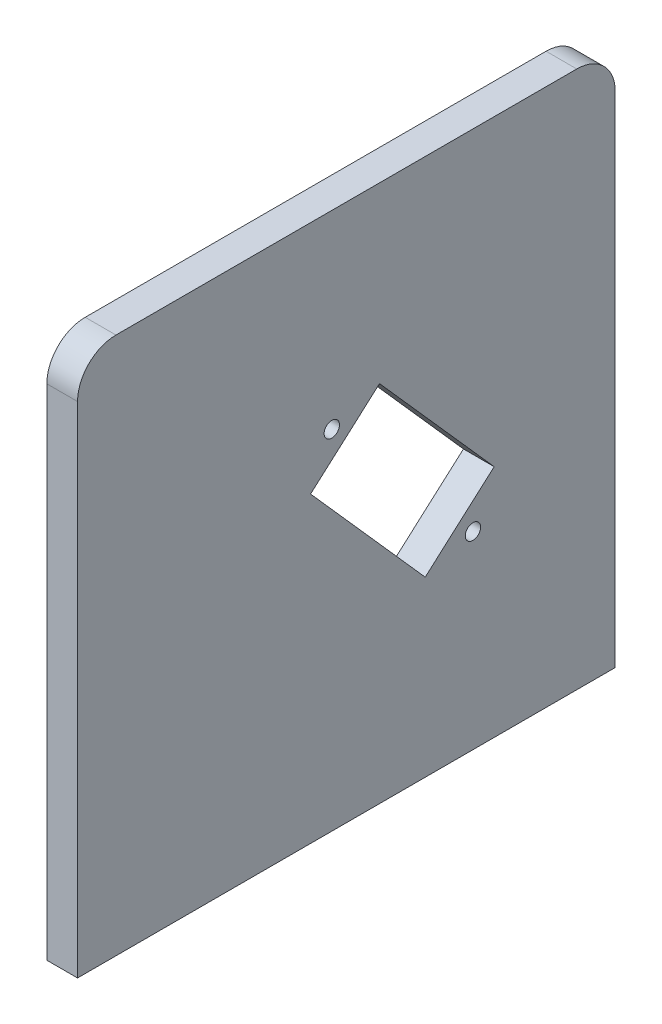
SolidWorks part; units mm, degrees
ref_plane "Front Plane" through (0, 0, 0) normal (0, 0, 1) x (1, 0, 0)
ref_plane "Top Plane" through (0, 0, 0) normal (0, 1, 0) x (1, 0, 0)
ref_plane "Right Plane" through (0, 0, 0) normal (1, 0, 0) x (0, 0, -1)
sketch "Sketch1" plane through (0, 0, 0) normal (0, 1, 0) x (1, 0, 0)
  line L5 (39.2287, 39.2125) -> (39.2287, -30.7875)
  line L9 (39.2287, 39.2125) -> (35.2287, 39.2125)
  line L10 (35.2287, 39.2125) -> (35.2287, -30.7875)
  line L11 (35.2287, -30.7875) -> (39.2287, -30.7875)
  dimension "D6" = 4
extrude "Boss-Extrude1" add sketch "Sketch1" along normal blind 3 contours L11 L10 L9 | L10 L11 L9 region at (37.2287, 0, -4.2125)
extrude "Boss-Extrude2" add sketch "Sketch1<3>" along normal blind 70
sketch "Sketch1<3>" plane through (0, 0, 0) normal (0, 1, 0) x (1, 0, 0) same geometry as "Sketch1"
extrude "Boss-Extrude3" add sketch "Sketch1<4>" along normal blind 70 rebuild error yes
sketch "Sketch1<4>" plane through (0, 0, 0) normal (0, 1, 0) x (1, 0, 0) same geometry as "Sketch1"
sketch "Sketch5" plane through (-50.7713, 0, 0) normal (-1, 0, 0) x (0, 0, 1)
  line L0 (-8.0225, 70) -> (-8.0225, 0) construction
  line L5 (-34.2125, 70) -> (-34.2125, 3) construction
  circle A0 centre (-8.0225, 60) radius 4
  dimension "D1" = 60
  dimension "D3" = 8
  dimension "D2" = 26.19
extrude "Cut-Extrude4" cut sketch "Sketch5" against normal blind 10 rebuild error yes
sketch "Sketch6" plane through (0, 3, 0) normal (0, 1, 0) x (1, 0, 0)
  line L0 (-50.7876, 44.2125) -> (49.2124, 44.2125) construction
  line L3 (-50.7876, -35.7875) -> (49.2124, -35.7875) construction
  line L8 (-50.7713, -40.7875) -> (39.2287, -40.7875) construction
  line L9 (-50.7713, 49.2125) -> (39.2287, 49.2125) construction
  circle A0 centre (-45.7876, -35.7875) radius 2.5
  circle A1 centre (-45.7876, 44.2125) radius 2.5
  circle A2 centre (43.7185, 44.2125) radius 2.5
  circle A3 centre (43.7185, -35.7875) radius 2.5
  dimension "D1" = 5
  dimension "D2" = 5
  dimension "D3" = 5
  dimension "D4" = 5
extrude "Cut-Extrude5" cut sketch "Sketch6" against normal blind 10 rebuild error yes
extrude "Boss-Extrude4" add sketch "Sketch1<5>" along normal blind 80 rebuild error yes
sketch "Sketch1<5>" plane through (0, 0, 0) normal (0, 1, 0) x (1, 0, 0) same geometry as "Sketch1"
extrude "Cut-Extrude6" cut sketch "Sketch5<2>" against normal blind 10 rebuild error yes
sketch "Sketch5<2>" plane through (-50.7713, 0, 0) normal (-1, 0, 0) x (0, 0, 1) same geometry as "Sketch5"
fillet "Fillet1" radius 3 rebuild error yes
fillet "Fillet2" radius 5 2 edges at (37.2287, 70, -39.2125) (37.2287, 70, 30.7875)
fillet "Fillet3" radius 4 rebuild error yes
sketch "Sketch7" plane through (39.2287, 0, 0) normal (1, 0, 0) x (0, 0, -1)
  line L0 (-30.7875, -10) -> (39.2125, -10) construction
  line L1 (-30.7875, 65) -> (-30.7875, 0) construction
  line L2 (39.2125, 65) -> (39.2125, 0) construction
  line L3 (-37.7875, 0) -> (46.2125, 0) construction
  circle A0 centre (27.4823, -10) radius 2.5
  dimension "D1" = 10
extrude "Cut-Extrude7" cut sketch "Sketch7" against normal blind 10 rebuild error yes
sketch "Sketch8" plane through (39.2287, 0, 0) normal (1, 0, 0) x (0, 0, -1)
  line L0 (39.2125, 20) -> (-30.7875, 20) construction
  line L1 (39.2125, 65) -> (39.2125, 0) construction
  line L2 (-30.7875, 65) -> (-30.7875, 0) construction
  line L3 (26.9146, 20) -> (8.0207, 38.8939) construction
  circle A0 centre (8.0207, 38.8939) radius 2.5
  dimension "D3" = 5
  dimension "D1" = 26.72
  dimension "D2" = 45
extrude "Cut-Extrude8" cut sketch "Sketch8" against normal blind 10
sketch "Sketch9" plane through (39.2287, 0, 0) normal (1, 0, 0) x (0, 0, -1)
  circle A1 centre (8.0207, 38.8939) radius 3.5
extrude "Cut-Extrude9" cut sketch "Sketch9" against normal up to surface (67.5 mm away) rebuild error yes
sketch "Sketch26" plane through (0, 3, 0) normal (0, 1, 0) x (1, 0, 0)
  line L0 (39.2287, 39.2125) -> (39.2287, 46.2125) construction
  line L1 (39.2287, -37.7875) -> (39.2287, -30.7875) construction
  circle A0 centre (34.2287, 44.2125) radius 2.5
  circle A2 centre (34.2287, -36.0634) radius 2.5
  dimension "D1" = 5
  dimension "D2" = 5
  dimension "D3" = 5
  dimension "D4" = 5
extrude "Cut-Extrude11" cut sketch "Sketch26" against normal blind 10 contours A2 | A0 rebuild error yes
sketch "Sketch27" plane through (0, 3, 0) normal (0, 1, 0) x (1, 0, 0)
  line L0 (-49.8926, 48.3339) -> (38.35, -39.9088) construction
  line L1 (38.35, 48.3339) -> (-49.8926, -39.9088) construction
  line L2 (7.7287, 4.2125) -> (-19.2713, 4.2125) construction
  line L3 (7.7287, 3.4625) -> (-19.2713, 3.4625)
  line L4 (7.7287, 4.9625) -> (-19.2713, 4.9625)
  line L5 (0.9787, -7.4788) -> (-12.5213, 15.9039) construction
  line L6 (0.3292, -7.8538) -> (-13.1708, 15.5289)
  line L7 (1.6282, -7.1038) -> (-11.8718, 16.2789)
  line L8 (-12.5213, -7.4788) -> (0.9787, 15.9039) construction
  line L9 (-13.1708, -7.1038) -> (0.3292, 16.2789)
  line L10 (-11.8718, -7.8538) -> (1.6282, 15.5289)
  line L11 (-19.2713, 4.2125) -> (7.7287, 4.2125) construction
  line L12 (-19.2713, 4.9625) -> (7.7287, 4.9625)
  line L13 (-19.2713, 3.4625) -> (7.7287, 3.4625)
  line L14 (-12.5213, 15.9039) -> (0.9787, -7.4788) construction
  line L15 (-11.8718, 16.2789) -> (1.6282, -7.1038)
  line L16 (-13.1708, 15.5289) -> (0.3292, -7.8538)
  line L17 (0.9787, 15.9039) -> (-12.5213, -7.4788) construction
  line L18 (1.6282, 15.5289) -> (-11.8718, -7.8538)
  line L19 (0.3292, 16.2789) -> (-13.1708, -7.1038)
  arc A0 (-47.7713, 49.2125) -> (-50.7713, 46.2125) centre (-47.7713, 46.2125) ccw construction
  arc A1 (36.2287, -40.7875) -> (39.2287, -37.7875) centre (36.2287, -37.7875) ccw construction
  arc A2 (39.2287, 46.2125) -> (36.2287, 49.2125) centre (36.2287, 46.2125) ccw construction
  arc A3 (-50.7713, -37.7875) -> (-47.7713, -40.7875) centre (-47.7713, -37.7875) ccw construction
  arc A4 (7.7287, 3.4625) -> (7.7287, 4.9625) centre (7.7287, 4.2125) ccw
  arc A5 (-19.2713, 4.9625) -> (-19.2713, 3.4625) centre (-19.2713, 4.2125) ccw
  circle A9 centre (-5.7713, 4.2125) radius 5.375
  arc A10 (0.3292, -7.8538) -> (1.6282, -7.1038) centre (0.9787, -7.4788) ccw
  arc A11 (-11.8718, 16.2789) -> (-13.1708, 15.5289) centre (-12.5213, 15.9039) ccw
  arc A12 (-13.1708, -7.1038) -> (-11.8718, -7.8538) centre (-12.5213, -7.4788) ccw
  arc A13 (1.6282, 15.5289) -> (0.3292, 16.2789) centre (0.9787, 15.9039) ccw
  arc A14 (-19.2713, 4.9625) -> (-19.2713, 3.4625) centre (-19.2713, 4.2125) ccw
  arc A15 (7.7287, 3.4625) -> (7.7287, 4.9625) centre (7.7287, 4.2125) ccw
  arc A16 (-11.8718, 16.2789) -> (-13.1708, 15.5289) centre (-12.5213, 15.9039) ccw
  arc A17 (0.3292, -7.8538) -> (1.6282, -7.1038) centre (0.9787, -7.4788) ccw
  arc A18 (1.6282, 15.5289) -> (0.3292, 16.2789) centre (0.9787, 15.9039) ccw
  arc A19 (-13.1708, -7.1038) -> (-11.8718, -7.8538) centre (-12.5213, -7.4788) ccw
  circle A20 centre (-5.7713, 4.2125) radius 2.75
  point P18 (-5.7713, 4.2125)
  point P30 (-5.7713, 4.2125)
  point P37 (-5.7713, 4.2125)
  point P44 (-5.7713, 4.2125)
  point P51 (-5.7713, 4.2125)
  point P58 (-5.7713, 4.2125)
  point P63 (-5.7713, 4.2125)
  dimension "D1" = 10.75
  dimension "D2" = 0.75
  dimension "D3" = 13.5
  dimension "D4" = 6
extrude "Cut-Extrude14" cut sketch "Sketch27" against normal blind 10 contours L3 A5 L4 A4 | L6 A11 L7 A10 | L10 A13 L9 A12 rebuild error yes
extrude "Cut-Extrude15" cut sketch "Sketch27<7>" against normal blind 10 contours L3 A20 L9 | L6 A20 L4 | L9 A20 L7 | L4 A20 L10 | L7 A20 L3 | L10 A20 L6 rebuild error yes
sketch "Sketch27<7>" plane through (0, 3, 0) normal (0, 1, 0) x (1, 0, 0) same geometry as "Sketch27"
sketch "Sketch28" plane through (-50.7713, 0, 0) normal (-1, 0, 0) x (0, 0, 1)
  line L0 (-23.4588, 51.635) -> (-8.5312, 68.47)
  line L1 (-8.5312, 68.47) -> (0.4475, 60.5086)
  line L2 (0.4475, 60.5086) -> (-14.4801, 43.6736)
  line L3 (-14.4801, 43.6736) -> (-23.4588, 51.635)
  line L4 (-8.0225, 60) -> (-12.6884, 54.7379) construction
  line L5 (-12.6884, 54.7379) -> (-25.2505, 40.5707) construction
  line L6 (-8.0225, 60) -> (2.1094, 71.4266) construction
  circle A0 centre (-8.0225, 60) radius 4 construction
  circle A1 centre (-8.0225, 60) radius 4
  circle A2 centre (-2.3169, 66.4347) radius 1
  circle A3 centre (-20.6944, 45.709) radius 1
  point P8 (-18.9694, 47.6543)
  dimension "D3" = 2
  dimension "D4" = 8.6
  dimension "D5" = 27.7
  dimension "D1" = 22.5
  dimension "D2" = 12
  dimension "D6" = 2.6
extrude "Cut-Extrude16" cut sketch "Sketch28" against normal up to surface (4 mm away) rebuild error yes
sketch "Sketch29" plane through (39.2287, 0, 0) normal (1, 0, 0) x (0, 0, -1)
  line L8 (8.0207, 38.8939) -> (0.0593, 47.8726) construction
  line L9 (0.0593, 47.8726) -> (37.8759, 5.2239) construction
  line L10 (8.5294, 47.3639) -> (23.457, 30.5289)
  line L11 (23.457, 30.5289) -> (14.4783, 22.5675)
  line L12 (14.4783, 22.5675) -> (-0.4493, 39.4025)
  line L13 (-0.4493, 39.4025) -> (8.5294, 47.3639)
  circle A6 centre (8.0207, 38.8939) radius 3.5 construction
  circle A7 centre (8.0207, 38.8939) radius 3.5
  circle A8 centre (2.3151, 45.3286) radius 1
  circle A9 centre (20.6926, 24.6028) radius 1
  point P4 (4.04, 43.3832)
  point P28 (18.9676, 26.5482)
  dimension "D4" = 2.6
  dimension "D5" = 27.7
  dimension "D6" = 2
  dimension "D7" = 2
  dimension "D2" = 12
  dimension "D3" = 22.5
  dimension "D8" = 8.6
extrude "Cut-Extrude18" cut sketch "Sketch29" against normal up to surface (4 mm away) up to face at (35.2287, 38.8939, -10.5207)
sketch "Sketch31" plane through (0, 3, 0) normal (0, 1, 0) x (1, 0, 0)
  circle A0 centre (-5.7713, 4.2125) radius 5.375
  dimension "D1" = 10.75
extrude "Cut-Extrude19" cut sketch "Sketch31" against normal blind 10 rebuild error yes
sketch "Sketch33" plane through (39.2287, 0, 0) normal (1, 0, 0) x (0, 0, -1)
  circle A0 centre (8.0207, 38.8939) radius 3.5 construction
  circle A1 centre (8.0207, 38.8939) radius 3.5
extrude "Cut-Extrude20" cut sketch "Sketch33" against normal through all
